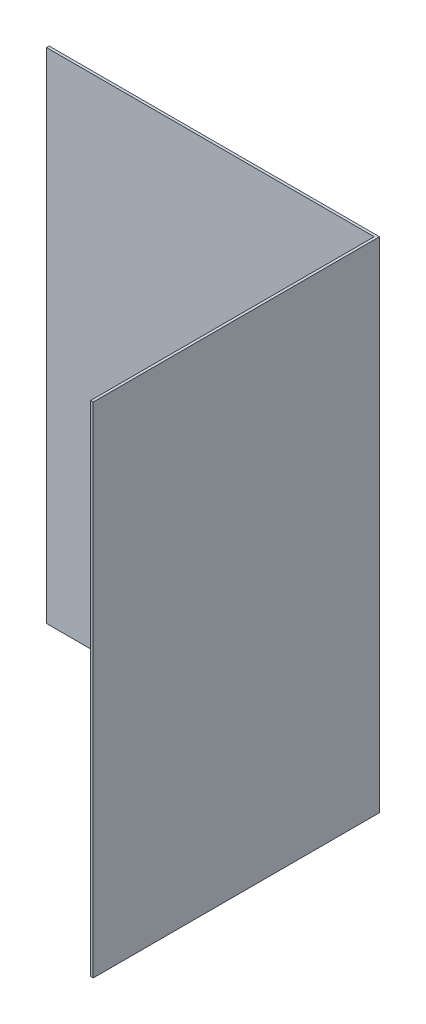
SolidWorks part; units mm, degrees
material "Copper"
ref_plane "Front Plane" through (0, 0, 0) normal (0, 0, 1) x (1, 0, 0)
ref_plane "Top Plane" through (0, 0, 0) normal (0, 1, 0) x (1, 0, 0)
ref_plane "Right Plane" through (0, 0, 0) normal (1, 0, 0) x (0, 0, -1)
sketch "Sketch1" plane through (0, 0, 0) normal (0, 0, 1) x (1, 0, 0)
  line L0 (15.875, 14.2939) -> (-15.875, 14.2939) construction
  line L1 (15.875, -14.4692) -> (-3.175, -14.4692)
  line L2 (15.875, -14.4692) -> (15.875, 14.2939)
  line L3 (15.875, 14.2939) -> (-3.175, 14.2939)
  line L4 (-3.175, -14.4692) -> (-3.175, 14.2939)
  line L5 (15.875, 38.1) -> (15.875, -38.1) construction
  circle A0 centre (9.525, 0) radius 1.5875 construction
  circle A1 centre (9.525, 0) radius 1.5875
  point P12 (0, 0)
  dimension "D1" = 19.05
extrude "Boss-Extrude1" add sketch "Sketch1" along normal blind 0.1524
sketch "Sketch2" plane through (0, 0, 0.1524) normal (0, 0, 1) x (1, 0, 0)
  line L0 (15.875, -14.4692) -> (-3.175, -14.4692) construction
  line L1 (15.875, 14.2939) -> (15.7226, 14.2939)
  line L2 (15.875, 14.2939) -> (15.875, -14.4692)
  line L3 (15.875, -14.4692) -> (15.7226, -14.4692)
  line L4 (15.7226, 14.2939) -> (15.7226, -14.4692)
  dimension ".006" = 0.1524
extrude "Boss-Extrude2" add sketch "Sketch2" along normal up to surface (16.3573 mm away)
